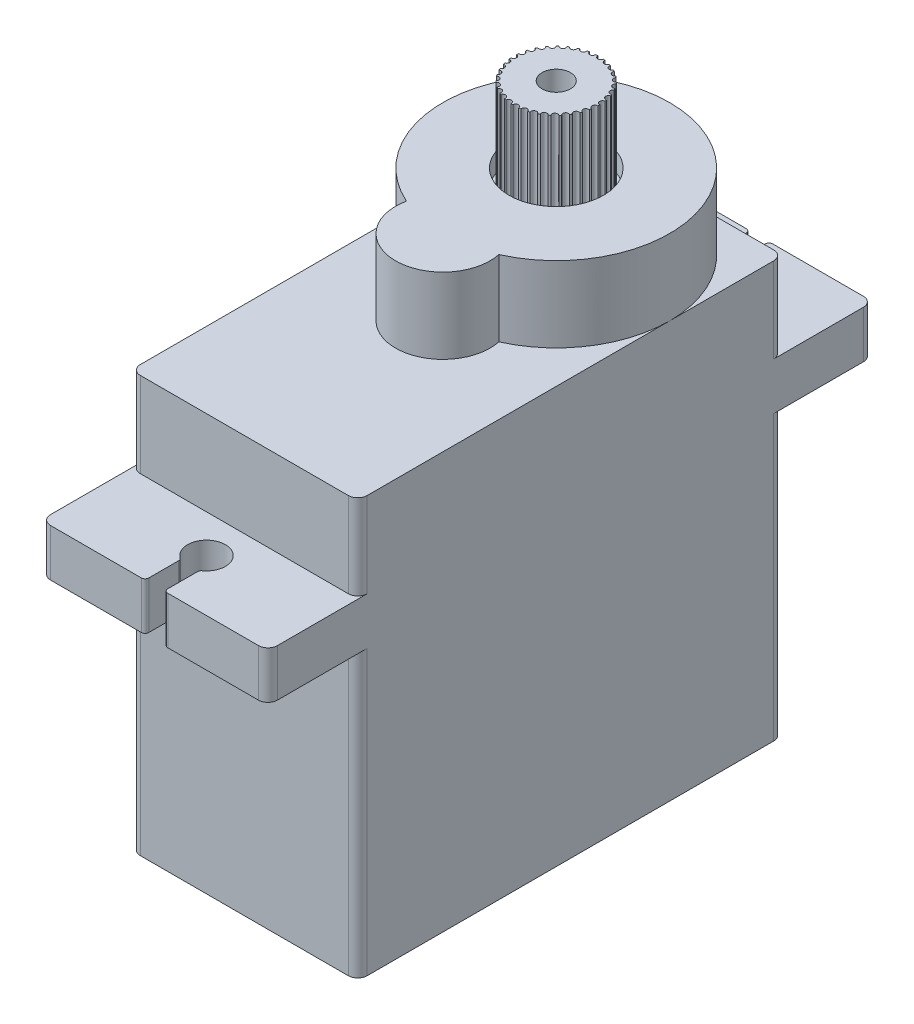
SolidWorks part; units mm, degrees
ref_plane "Ön Düzlem" through (0, 0, 0) normal (0, 0, 1) x (1, 0, 0)
ref_plane "Üst Düzlem" through (0, 0, 0) normal (0, 1, 0) x (1, 0, 0)
ref_plane "Sağ Düzlem" through (0, 0, 0) normal (1, 0, 0) x (0, 0, -1)
sketch "Çizim1" plane through (0, 0, 0) normal (0, 1, 0) x (1, 0, 0)
  line L1 (-5.5, 11.25) -> (5.5, 11.25)
  line L2 (-6, 10.75) -> (-6, -10.75)
  line L3 (-5.5, -11.25) -> (5.5, -11.25)
  line L4 (6, 10.75) -> (6, -10.75)
  line L5 (-6, 11.25) -> (6, -11.25) construction
  line L6 (-6, -11.25) -> (6, 11.25) construction
  arc A0 (5.5, -11.25) -> (6, -10.75) centre (5.5, -10.75) ccw
  arc A1 (-6, -10.75) -> (-5.5, -11.25) centre (-5.5, -10.75) ccw
  arc A2 (5.5, 11.25) -> (6, 10.75) centre (5.5, 10.75) cw
  arc A3 (-5.5, 11.25) -> (-6, 10.75) centre (-5.5, 10.75) ccw
  point P0 (0, 0)
  dimension "D3" = 0.5
  dimension "D1" = 12
  dimension "D2" = 22.5
extrude "Yükseklik-Ekstrüzyon1" add sketch "Çizim1" along normal blind 1
sketch "Çizim2" plane through (0, 1, 0) normal (0, 1, 0) x (1, 0, 0)
  line L0 (-5, 9.25) -> (-5, -9.25)
  line L1 (-5.5, 11.25) -> (5.5, 11.25)
  line L2 (-6, 10.75) -> (-6, -10.75)
  line L3 (-5.5, -11.25) -> (5.5, -11.25)
  line L4 (6, 10.75) -> (6, -10.75)
  line L5 (-6, 11.25) -> (-5.8961, 11.0552) construction
  line L6 (-6, -11.25) -> (-5.8961, -11.0552) construction
  line L7 (-4, -10.25) -> (4, -10.25)
  line L8 (5, 9.25) -> (5, -9.25)
  line L9 (-4, 10.25) -> (4, 10.25)
  line L10 (-6, -11.25) -> (6, -11.25) construction
  line L11 (6, 11.25) -> (6, -11.25) construction
  line L12 (-6, 11.25) -> (-6, -11.25) construction
  line L13 (-6, 11.25) -> (6, 11.25) construction
  line L14 (-5, 10.25) -> (5, 10.25) construction
  line L15 (-5, 10.25) -> (-5, -10.25) construction
  line L16 (-4.9345, 9.2521) -> (4.9345, -9.2521) construction
  line L17 (5, 10.25) -> (5, -10.25) construction
  line L18 (5.8961, 11.0552) -> (6, 11.25) construction
  line L19 (-5, -10.25) -> (5, -10.25) construction
  line L20 (5.8961, -11.0552) -> (6, -11.25) construction
  line L21 (-4.9345, -9.2521) -> (4.9345, 9.2521) construction
  arc A0 (5.5, -11.25) -> (6, -10.75) centre (5.5, -10.75) ccw
  arc A1 (-6, -10.75) -> (-5.5, -11.25) centre (-5.5, -10.75) ccw
  arc A2 (5.5, 11.25) -> (6, 10.75) centre (5.5, 10.75) cw
  arc A3 (-5.5, 11.25) -> (-6, 10.75) centre (-5.5, 10.75) ccw
  arc A5 (4, 10.25) -> (5, 9.25) centre (5, 10.25) ccw
  arc A7 (-4, -10.25) -> (-5, -9.25) centre (-5, -10.25) ccw
  arc A8 (-5, 9.25) -> (-4, 10.25) centre (-5, 10.25) ccw
  arc A9 (5, -9.25) -> (4, -10.25) centre (5, -10.25) ccw
  point P0 (0, 0)
  dimension "D2" = 0.5
  dimension "D1" = 1
extrude "Yükseklik-Ekstrüzyon2" add sketch "Çizim2" along normal blind 5
sketch "Çizim3" plane through (0, 6, 0) normal (0, 1, 0) x (1, 0, 0)
  line L0 (0, -10.25) -> (0, -11.25) construction
  line L1 (-4, -10.25) -> (4, -10.25) construction
  line L2 (-5.5, -11.25) -> (5.5, -11.25) construction
  line L3 (0, -11.25) -> (0, -10.75) construction
  line L4 (0, -10.75) -> (2.4368, -10.75) construction
  line L6 (-2, -10.25) -> (2, -10.25)
  line L7 (-2, -10.25) -> (-2, -11.25)
  line L8 (-2, -11.25) -> (2, -11.25)
  line L9 (2, -10.25) -> (2, -11.25)
  line L10 (-2, -10.25) -> (2, -11.25) construction
  line L11 (-2, -11.25) -> (2, -10.25) construction
  dimension "D1" = 4
extrude "Kes-Ekstrüzyon1" cut sketch "Çizim3" against normal blind 1
fillet "Radyus1" radius 0.1 2 edges at (2, 5, 10.75) (-2, 5, 10.75)
sketch "Çizim4" plane through (0, 6, 0) normal (0, 1, 0) x (1, 0, 0)
  line L0 (-4, 10.25) -> (4, 10.25)
  line L1 (-5.5, 11.25) -> (5.5, 11.25)
  line L2 (-6, 10.75) -> (-6, -10.75)
  line L3 (-5.5, -11.25) -> (5.5, -11.25)
  line L4 (6, 10.75) -> (6, -10.75)
  line L5 (-6, 11.25) -> (-5.8961, 11.0552) construction
  line L6 (-6, -11.25) -> (-5.8961, -11.0552) construction
  line L7 (-4, 10.25) -> (4, 10.25)
  line L8 (5, 9.25) -> (5, -9.25)
  line L9 (5, -9.25) -> (5, 9.25)
  line L10 (-4, 10.25) -> (4, 10.25)
  line L11 (5, 9.25) -> (5, -9.25)
  line L12 (-4, -10.25) -> (4, -10.25)
  line L13 (-5, 9.25) -> (-5, -9.25)
  line L14 (-4.9345, 9.2521) -> (4.9345, -9.2521) construction
  line L15 (-5, 10.25) -> (-5, -10.25) construction
  line L16 (-5, 10.25) -> (5, 10.25) construction
  line L17 (5, 10.25) -> (5, -10.25) construction
  line L18 (5.8961, 11.0552) -> (6, 11.25) construction
  line L19 (5.8961, -11.0552) -> (6, -11.25) construction
  line L20 (-5, -10.25) -> (5, -10.25) construction
  line L21 (-4.9345, -9.2521) -> (4.9345, 9.2521) construction
  arc A0 (5.5, -11.25) -> (6, -10.75) centre (5.5, -10.75) ccw
  arc A1 (-6, -10.75) -> (-5.5, -11.25) centre (-5.5, -10.75) ccw
  arc A2 (5.5, 11.25) -> (6, 10.75) centre (5.5, 10.75) cw
  arc A3 (-5.5, 11.25) -> (-6, 10.75) centre (-5.5, 10.75) ccw
  arc A4 (-5, 9.25) -> (-4, 10.25) centre (-5, 10.25) ccw
  arc A5 (4, 10.25) -> (5, 9.25) centre (5, 10.25) ccw
  arc A6 (-4, -10.25) -> (-5, -9.25) centre (-5, -10.25) ccw
  arc A7 (5, -9.25) -> (4, -10.25) centre (5, -10.25) ccw
  arc A8 (5, 10.25) -> (5, 10.25) centre (5, 10.25) cw
  arc A9 (5, -10.25) -> (5, -10.25) centre (5, -10.25) ccw
  arc A10 (-5, -10.25) -> (-5, -10.25) centre (-5, -10.25) ccw
  arc A11 (-5, 10.25) -> (-5, 10.25) centre (-5, 10.25) ccw
  point P0 (0, 0)
  line M12 (4, -10.25) -> (2, -10.25)
  line M14 (2, -11.25) -> (5.5, -11.25)
  arc M15 (5.5, -11.25) -> (6, -10.75) centre (5.5, -10.75) ccw
  line M16 (6, -10.75) -> (6, 10.75)
  arc M17 (6, 10.75) -> (5.5, 11.25) centre (5.5, 10.75) ccw
  line M18 (5.5, 11.25) -> (-5.5, 11.25)
  arc M19 (-5.5, 11.25) -> (-6, 10.75) centre (-5.5, 10.75) ccw
  line M20 (-6, 10.75) -> (-6, -10.75)
  arc M21 (-6, -10.75) -> (-5.5, -11.25) centre (-5.5, -10.75) ccw
  line M22 (-5.5, -11.25) -> (-2, -11.25)
  line M24 (-2, -10.25) -> (-4, -10.25)
  arc M25 (-4, -10.25) -> (-5, -9.25) centre (-5, -10.25) ccw
  line M26 (-5, -9.25) -> (-5, 9.25)
  arc M27 (-5, 9.25) -> (-4, 10.25) centre (-5, 10.25) ccw
  line M28 (-4, 10.25) -> (4, 10.25)
  arc M29 (4, 10.25) -> (5, 9.25) centre (5, 10.25) ccw
  line M30 (5, 9.25) -> (5, -9.25)
  arc M31 (5, -9.25) -> (4, -10.25) centre (5, -10.25) ccw
  dimension "D1" = 0.5
  dimension "D2" = 1
extrude "Yükseklik-Ekstrüzyon4" add sketch "Çizim4" along normal blind 9 contours M31 M12 M14 M15 M16 M17 M18 M19 M20 M21 M22 M24 M25 M26 M27 M28 M29 M30 | L12 L3 region at (0, 6, -10.995)
sketch "Çizim6" plane through (0, 15, 0) normal (0, 1, 0) x (1, 0, 0)
  line L0 (0, -10.25) -> (0, -12.25) construction
  line L1 (-5.5, 16) -> (-0.7, 16)
  line L2 (-6, 15.5) -> (-6, -15.5)
  line L3 (-5.5, -16) -> (-0.7, -16)
  line L4 (6, 15.5) -> (6, -15.5)
  line L5 (-6, 16) -> (6, -16) construction
  line L6 (-3.8437, -10.25) -> (6, 16) construction
  line L7 (-4, 10.25) -> (4, 10.25)
  line L8 (-5, 9.25) -> (-5, -9.25)
  line L9 (-4, -10.25) -> (4, -10.25)
  line L10 (5, 9.25) -> (5, -9.25)
  line L11 (-4.5616, 9.3512) -> (4.5616, -9.3512) construction
  line L12 (-4.5616, -9.3512) -> (4.5616, 9.3512) construction
  line L13 (0, -12.25) -> (0, -11.25) construction
  line L14 (-5.5, -11.25) -> (5.5, -11.25) construction
  line L15 (0, -11.25) -> (8.7476, -11.25) construction
  line L16 (0, -12.25) -> (8.7476, -12.25) construction
  line L17 (0.7, -16) -> (5.5, -16)
  line L18 (-0.5, -14.2247) -> (-0.5, -15.8)
  line L19 (0.5, -14.2247) -> (0.5, -15.8)
  line L20 (0, 0) -> (5, 0) construction
  line L21 (0.5, 14.2247) -> (0.5, 15.8)
  line L22 (-0.5, 14.2247) -> (-0.5, 15.8)
  line L23 (0.7, 16) -> (5.5, 16)
  arc A0 (-5, 9.25) -> (-4, 10.25) centre (-5, 10.25) ccw
  arc A1 (4, 10.25) -> (5, 9.25) centre (5, 10.25) ccw
  arc A2 (5, -9.25) -> (4, -10.25) centre (5, -10.25) ccw
  arc A3 (-4, -10.25) -> (-5, -9.25) centre (-5, -10.25) ccw
  arc A4 (5.5, -16) -> (6, -15.5) centre (5.5, -15.5) ccw
  arc A5 (-6, -15.5) -> (-5.5, -16) centre (-5.5, -15.5) ccw
  arc A6 (5.5, 16) -> (6, 15.5) centre (5.5, 15.5) cw
  arc A7 (-5.5, 16) -> (-6, 15.5) centre (-5.5, 15.5) ccw
  arc A9 (0.5833, -14.0622) -> (-0.5833, -14.0622) centre (0, -13.25) ccw
  arc A10 (0.5, -14.2247) -> (0.5833, -14.0622) centre (0.7, -14.2247) cw
  arc A11 (-0.5, -14.2247) -> (-0.5833, -14.0622) centre (-0.7, -14.2247) ccw
  arc A12 (0.5, -15.8) -> (0.7, -16) centre (0.7, -15.8) ccw
  arc A13 (-0.5, -15.8) -> (-0.7, -16) centre (-0.7, -15.8) cw
  arc A14 (0.5, 15.8) -> (0.7, 16) centre (0.7, 15.8) cw
  arc A15 (-0.5, 15.8) -> (-0.7, 16) centre (-0.7, 15.8) ccw
  arc A16 (0.5, 14.2247) -> (0.5833, 14.0622) centre (0.7, 14.2247) ccw
  arc A17 (-0.5, 14.2247) -> (-0.5833, 14.0622) centre (-0.7, 14.2247) cw
  arc A18 (0.5833, 14.0622) -> (-0.5833, 14.0622) centre (0, 13.25) cw
  point P0 (0, 0)
  point P6 (0, 0)
  point P54 (0.5, -16)
  dimension "D2" = 0.5
  dimension "D4" = 2
  dimension "D5" = 0.2
  dimension "D1" = 32
  dimension "D3" = 1
extrude "Yükseklik-Ekstrüzyon5" add sketch "Çizim6" along normal blind 2.5
sketch "Çizim7" plane through (0, 17.5, 0) normal (0, 1, 0) x (1, 0, 0)
  line L0 (6, -15.5) -> (6, 15.5) construction
  line L1 (-5.5, 11.25) -> (5.5, 11.25)
  line L2 (-6, 10.75) -> (-6, -10.75)
  line L3 (-5.5, -11.25) -> (5.5, -11.25)
  line L4 (6, 10.75) -> (6, -10.75)
  line L5 (-6, 11.25) -> (-5.8961, 11.0552) construction
  line L6 (-6, -11.25) -> (-5.8961, -11.0552) construction
  line L7 (-5, 9.25) -> (-5, -9.25)
  line L8 (-4, 10.25) -> (4, 10.25)
  line L9 (5, 9.25) -> (5, -9.25)
  line L10 (4, -10.25) -> (-4, -10.25)
  line L12 (-4.9345, 9.2521) -> (4.9345, -9.2521) construction
  line L13 (5.8961, 11.0552) -> (6, 11.25) construction
  line L14 (5.8961, -11.0552) -> (6, -11.25) construction
  line L15 (-5, -9.25) -> (-5, 9.25)
  line L16 (-4.9345, -9.2521) -> (4.9345, 9.2521) construction
  line L17 (-5, 9.25) -> (-5, -9.25)
  arc A0 (-6, -10.75) -> (-5.5, -11.25) centre (-5.5, -10.75) ccw
  arc A1 (5.5, -11.25) -> (6, -10.75) centre (5.5, -10.75) ccw
  arc A2 (5.5, 11.25) -> (6, 10.75) centre (5.5, 10.75) cw
  arc A3 (-5.5, 11.25) -> (-6, 10.75) centre (-5.5, 10.75) ccw
  arc A4 (-5, 9.25) -> (-4, 10.25) centre (-5, 10.25) ccw
  arc A5 (4, 10.25) -> (5, 9.25) centre (5, 10.25) ccw
  arc A6 (5, -9.25) -> (4, -10.25) centre (5, -10.25) ccw
  arc A8 (-4, -10.25) -> (-5, -9.25) centre (-5, -10.25) ccw
  point P0 (0, 0)
  line M16 (6, -15.5) -> (6, 15.5)
  line M28 (-6, 15.5) -> (-6, -15.5)
  line M39 (-5, -9.25) -> (-5, 9.25)
  arc M40 (-5, 9.25) -> (-4, 10.25) centre (-5, 10.25) ccw
  line M41 (-4, 10.25) -> (4, 10.25)
  arc M42 (4, 10.25) -> (5, 9.25) centre (5, 10.25) ccw
  line M43 (5, 9.25) -> (5, -9.25)
  arc M44 (5, -9.25) -> (4, -10.25) centre (5, -10.25) ccw
  line M45 (4, -10.25) -> (-4, -10.25)
  arc M46 (-4, -10.25) -> (-5, -9.25) centre (-5, -10.25) ccw
  dimension "D2" = 0.5
  dimension "D1" = 22.5
extrude "Yükseklik-Ekstrüzyon6" add sketch "Çizim7" along normal blind 3.5 contours L1 A3 A0 L3 A1 A2 M28 M16 M46 M39 M40 M41 M42 M43 M44 M45 region at (0, 17.5, -10.995)
sketch "Çizim8" plane through (0, 21, 0) normal (0, 1, 0) x (1, 0, 0)
  line L0 (6, -15.5) -> (6, -10.75) construction
  line L1 (-5.5, 11.25) -> (5.5, 11.25)
  line L2 (-6, 10.75) -> (-6, -10.75)
  line L3 (-5.5, -11.25) -> (5.5, -11.25)
  line L4 (6, 10.75) -> (6, -10.75)
  line L5 (-6, 11.25) -> (6, -11.25) construction
  line L6 (-6, -11.25) -> (6, 11.25) construction
  arc A0 (-6, -10.75) -> (-5.5, -11.25) centre (-5.5, -10.75) ccw
  arc A1 (5.5, -11.25) -> (6, -10.75) centre (5.5, -10.75) ccw
  arc A2 (5.5, 11.25) -> (6, 10.75) centre (5.5, 10.75) cw
  arc A3 (-5.5, 11.25) -> (-6, 10.75) centre (-5.5, 10.75) ccw
  point P0 (0, 0)
  dimension "D1" = 0.5
extrude "Yükseklik-Ekstrüzyon7" add sketch "Çizim8" along normal blind 1
sketch "Çizim9" plane through (0, 22, 0) normal (0, 1, 0) x (1, 0, 0)
  line L0 (-6, 5.25) -> (6, 5.25) construction
  line L1 (-6, 10.75) -> (-6, -10.75) construction
  line L2 (6, -10.75) -> (6, 10.75) construction
  line L3 (5.5, 11.25) -> (-5.5, 11.25) construction
  line L4 (0, 5.25) -> (0, -0.75) construction
  arc A0 (2.4451, -0.2292) -> (-2.4451, -0.2292) centre (0, 5.25) ccw
  arc A1 (-2.4451, -0.2292) -> (2.4451, -0.2292) centre (0, -0.75) ccw
  arc A2 (1.0153, 0.3542) -> (-1.0153, 0.3542) centre (0, 5.25) ccw
  arc A3 (-1.0153, 0.3542) -> (1.0153, 0.3542) centre (0, -0.75) ccw
  dimension "D2" = 5
  dimension "D1" = 6
  dimension "D3" = 1
extrude "Kes-Ekstrüzyon2" cut sketch "Çizim9" against normal blind 1 contours A2 A3
extrude "Yükseklik-Ekstrüzyon8" add sketch "Çizim9<3>" along normal blind 3
sketch "Çizim9<3>" plane through (0, 22, 0) normal (0, 1, 0) x (1, 0, 0) same geometry as "Çizim9"
fillet "Radyus2" radius 0.5 2 edges at (1.0153, 23, -0.3542) (-1.0153, 23, -0.3542)
sketch "Çizim10" plane through (0, 25, 0) normal (0, 1, 0) x (1, 0, 0)
  arc A0 (2.4451, -0.2292) -> (-2.4451, -0.2292) centre (0, 5.25) ccw
  arc A1 (-2.4451, -0.2292) -> (2.4451, -0.2292) centre (0, -0.75) ccw
extrude "Yükseklik-Ekstrüzyon9" add sketch "Çizim10" along normal blind 1
sketch "Çizim11" plane through (0, 26, 0) normal (0, 1, 0) x (1, 0, 0)
  circle A0 centre (0, 5.25) radius 2.5
  dimension "D1" = 5
extrude "Kes-Ekstrüzyon3" cut sketch "Çizim11" against normal blind 10
sketch "Çizim15" plane through (0, 26, 0) normal (0, 1, 0) x (1, 0, 0)
  circle A0 centre (0, -0.75) radius 0.25
  dimension "D1" = 0.5
extrude "Yükseklik-Ekstrüzyon12" add sketch "Çizim15" against normal blind 11
ref_plane "Düzlem3" through (0, 30, 0) normal (0, 1, 0) x (1, 0, 0)
sketch "Çizim19" plane through (0, 30, 0) normal (0, 1, 0) x (1, 0, 0)
  circle A0 centre (0, 5.25) radius 2.25
  dimension "D1" = 4.5
extrude "Yükseklik-Ekstrüzyon17" add sketch "Çizim19" against normal blind 5 separate body
sketch "Çizim20" plane through (0, 25, 0) normal (0, -1, 0) x (1, 0, 0)
  circle A0 centre (0, -5.25) radius 4.75
  dimension "D1" = 9.5
extrude "Yükseklik-Ekstrüzyon18" add sketch "Çizim20" along normal blind 3
sketch "Çizim21" plane through (0, 30, 0) normal (0, 1, 0) x (1, 0, 0)
  circle A0 centre (0, 5.25) radius 0.75
  dimension "D1" = 1.5
extrude "Kes-Ekstrüzyon5" cut sketch "Çizim21" against normal blind 10
ref_plane "Düzlem4" through (0, 25.5, 0) normal (0, 1, 0) x (1, 0, 0)
sketch "Çizim22" plane through (0, 25.5, 0) normal (0, 1, 0) x (1, 0, 0)
  line L0 (0, 11.25) -> (0, -3.25) construction
  arc A0 (2.4451, -0.2292) -> (-2.4451, -0.2292) centre (0, 5.25) ccw construction
  arc A1 (-2.4451, -0.2292) -> (2.4451, -0.2292) centre (0, -0.75) ccw construction
  circle A2 centre (0, -0.75) radius 0.5
  dimension "D1" = 1
extrude "Yükseklik-Ekstrüzyon19" add sketch "Çizim22" against normal blind 5
sketch "Çizim23" plane through (0, 20.5, 0) normal (0, -1, 0) x (1, 0, 0)
  circle A0 centre (0, 0.75) radius 4
  dimension "D1" = 8
extrude "Yükseklik-Ekstrüzyon20" add sketch "Çizim23" along normal blind 2
sketch "Çizim24" plane through (0, 22, 0) normal (0, -1, 0) x (1, 0, 0)
  circle A0 centre (0, -5.25) radius 0.75
extrude "Yükseklik-Ekstrüzyon21" add sketch "Çizim24" along normal blind 7 separate body
ref_plane "Düzlem5" through (0, 19, 0) normal (0, -1, 0) x (-1, 0, 0)
sketch "Çizim25" plane through (0, 19, 0) normal (0, -1, 0) x (-1, 0, 0)
  circle A0 centre (0, 5.25) radius 3.5
  dimension "D1" = 7
extrude "Yükseklik-Ekstrüzyon22" add sketch "Çizim25" along normal blind 1
ref_plane "Düzlem6" through (0, 17.5, 0) normal (0, -1, 0) x (-1, 0, 0)
sketch "Çizim26" plane through (0, 17.5, 0) normal (0, -1, 0) x (-1, 0, 0)
  circle A0 centre (0, -0.75) radius 4.5
  dimension "D1" = 9
extrude "Yükseklik-Ekstrüzyon23" add sketch "Çizim26" along normal blind 1
sketch "Çizim32" plane through (0, 0, 10.25) normal (0, 0, -1) x (-1, 0, 0)
  line L1 (2, 6) -> (-2, 6)
  line L2 (2, 6) -> (2, 5.1)
  line L3 (1.9, 5) -> (-1.9, 5)
  line L4 (-2, 6) -> (-2, 5.1)
  arc A0 (-1.9, 5) -> (-2, 5.1) centre (-1.9, 5.1) cw
  arc A1 (2, 5.1) -> (1.9, 5) centre (1.9, 5.1) cw
  point P7 (-2, 5)
  dimension "D3" = 0.1
  dimension "D1" = 1
  dimension "D2" = 4
extrude "Kes-Ekstrüzyon7" cut sketch "Çizim32" along normal blind 30
sketch "Çizim33" plane through (0, 0, 11.25) normal (0, 0, 1) x (1, 0, 0)
  line L1 (-2, 6) -> (2, 6)
  line L2 (-2, 6) -> (-2, 5.1)
  line L3 (-1.9, 5) -> (1.9, 5)
  line L4 (2, 6) -> (2, 5.1)
  arc A0 (1.9, 5) -> (2, 5.1) centre (1.9, 5.1) ccw
  arc A1 (-2, 5.1) -> (-1.9, 5) centre (-1.9, 5.1) ccw
  point P7 (2, 5)
  point P10 (-2, 5)
  dimension "D3" = 0.1
  dimension "D1" = 1
  dimension "D2" = 4
extrude "Yükseklik-Ekstrüzyon33" add sketch "Çizim33" against normal blind 1
sketch "Çizim34" plane through (0, 1, 0) normal (0, 1, 0) x (1, 0, 0)
  line L0 (-5, -6.25) -> (5, -6.25) construction
  line L1 (-5, 9.25) -> (-5, -9.25) construction
  line L2 (5, -9.25) -> (5, 9.25) construction
  line L3 (-4, -10.25) -> (4, -10.25) construction
  line L5 (-3, -3.25) -> (3, -3.25)
  line L6 (-4, -4.25) -> (-4, -8.25)
  line L7 (-3, -9.25) -> (3, -9.25)
  line L8 (4, -4.25) -> (4, -8.25)
  line L9 (-4, -3.25) -> (4, -9.25) construction
  line L10 (-4, -9.25) -> (4, -3.25) construction
  arc A0 (3, -9.25) -> (4, -8.25) centre (3, -8.25) ccw
  arc A1 (-4, -8.25) -> (-3, -9.25) centre (-3, -8.25) ccw
  arc A2 (3, -3.25) -> (4, -4.25) centre (3, -4.25) cw
  arc A3 (-3, -3.25) -> (-4, -4.25) centre (-3, -4.25) ccw
  point P8 (0, -6.25)
  dimension "D4" = 1
  dimension "D1" = 4
  dimension "D2" = 6
  dimension "D3" = 8
extrude "Yükseklik-Ekstrüzyon34" add sketch "Çizim34" along normal blind 14
ref_plane "Düzlem8" through (0, 1, 0) normal (0, -1, 0) x (-1, 0, 0)
sketch "Çizim37" plane through (0, 1, 0) normal (0, -1, 0) x (-1, 0, 0)
  line L0 (4, -6.25) -> (-4, -6.25) construction
  line L1 (4, -4.25) -> (4, -8.25) construction
  line L2 (-4, -8.25) -> (-4, -4.25) construction
  line L4 (4, -9.25) -> (-4, -9.25)
  line L5 (4, -9.25) -> (4, -3.25)
  line L6 (4, -3.25) -> (-4, -3.25)
  line L7 (-4, -9.25) -> (-4, -3.25)
  line L8 (4, -9.25) -> (-4, -3.25) construction
  line L9 (4, -3.25) -> (-4, -9.25) construction
  point P6 (0, -6.25)
  dimension "D1" = 6
  dimension "D2" = 8
extrude "Yükseklik-Ekstrüzyon36" add sketch "Çizim37" against normal blind 1
ref_plane "Düzlem9" through (0, 0, -10.75) normal (0, 0, -1) x (-1, 0, 0)
sketch "Çizim39" plane through (0, 0, -10.75) normal (0, 0, -1) x (-1, 0, 0)
  line L0 (0, 0) -> (0, 6.0146) construction
  line L1 (-5.5, 0) -> (5.5, 0) construction
  line L2 (-2, 6.0146) -> (2, 6.0146)
  line L4 (-2, 6.0146) -> (-2, 5.0146)
  line L5 (-2, 5.0146) -> (2, 5.0146)
  line L6 (2, 6.0146) -> (2, 5.0146)
  line L7 (0, 6.0146) -> (2, 5.0146) construction
  line L8 (-2, 5.0146) -> (0, 6.0146) construction
extrude "Yükseklik-Ekstrüzyon37" add sketch "Çizim39" along normal blind 0.1
sketch "Çizim40" plane through (0, 0, -10.85) normal (0, 0, -1) x (-1, 0, 0)
  line L0 (-2, 5.55) -> (2, 5.55) construction
  line L1 (-2, 6) -> (-2, 5.1) construction
  line L2 (2, 5.1) -> (2, 6) construction
  circle A0 centre (0, 5.55) radius 0.4
  circle A1 centre (1, 5.55) radius 0.4
  circle A2 centre (-1, 5.55) radius 0.4
  dimension "D1" = 0.8
  dimension "D2" = 1
  dimension "D3" = 1
extrude "Yükseklik-Ekstrüzyon38" add sketch "Çizim40" along normal blind 2
sketch "Çizim41" plane through (0, 30, 0) normal (0, 1, 0) x (1, 0, 0)
  line L0 (0, 5.25) -> (-2.25, 5.25) construction
  circle A0 centre (0, 5.25) radius 2.25
  circle A1 centre (-2.25, 5.25) radius 0.15
  circle A2 centre (-2.2138, 5.6518) radius 0.15
  circle A3 centre (-2.1065, 6.0406) radius 0.15
  circle A4 centre (-1.9315, 6.404) radius 0.15
  circle A5 centre (-1.6944, 6.7304) radius 0.15
  circle A6 centre (-1.4029, 7.0091) radius 0.15
  circle A7 centre (-1.0662, 7.2313) radius 0.15
  circle A8 centre (-0.6953, 7.3899) radius 0.15
  circle A9 centre (-0.302, 7.4796) radius 0.15
  circle A10 centre (0.1009, 7.4977) radius 0.15
  circle A11 centre (0.5007, 7.4436) radius 0.15
  circle A12 centre (0.8843, 7.3189) radius 0.15
  circle A13 centre (1.2395, 7.1278) radius 0.15
  circle A14 centre (1.5549, 6.8763) radius 0.15
  circle A15 centre (1.8203, 6.5725) radius 0.15
  circle A16 centre (2.0272, 6.2262) radius 0.15
  circle A17 centre (2.1689, 5.8486) radius 0.15
  circle A18 centre (2.2409, 5.4517) radius 0.15
  circle A19 centre (2.2409, 5.0483) radius 0.15
  circle A20 centre (2.1689, 4.6514) radius 0.15
  circle A21 centre (2.0272, 4.2738) radius 0.15
  circle A22 centre (1.8203, 3.9275) radius 0.15
  circle A23 centre (1.5549, 3.6237) radius 0.15
  circle A24 centre (1.2395, 3.3722) radius 0.15
  circle A25 centre (0.8843, 3.1811) radius 0.15
  circle A26 centre (0.5007, 3.0564) radius 0.15
  circle A27 centre (0.1009, 3.0023) radius 0.15
  circle A28 centre (-0.302, 3.0204) radius 0.15
  circle A29 centre (-0.6953, 3.1101) radius 0.15
  circle A30 centre (-1.0662, 3.2687) radius 0.15
  circle A31 centre (-1.4029, 3.4909) radius 0.15
  circle A32 centre (-1.6944, 3.7696) radius 0.15
  circle A33 centre (-1.9315, 4.096) radius 0.15
  circle A34 centre (-2.1065, 4.4594) radius 0.15
  circle A35 centre (-2.2138, 4.8482) radius 0.15
  point P75 (0, 5.25)
  circle M3 centre (0, 5.25) radius 2.25
  dimension "D1" = 0.3
  dimension "D2" = 35
extrude "Kes-Ekstrüzyon8" cut sketch "Çizim41" against normal blind 5 contours A1 A0 M3 | A1 L0 A0 | L0 A1 M3 | A3 | A2 | A35 | A34 | A33 | A32 | A31 | A30 | A29 | A28 | A27 | A26 | A25 | A24 | A23 | A22 | A21 | A20 | A19 | A18 | A17 | A16 | A15 | A14 | A13 | A12 | A11 | A10 | A9 | A8 | A7 | A6 | A5 | A4 region at (-2.1854, 30, -5.187) region at (-2.1854, 30, -5.313) region at (-2.3128, 30, -5.25)
